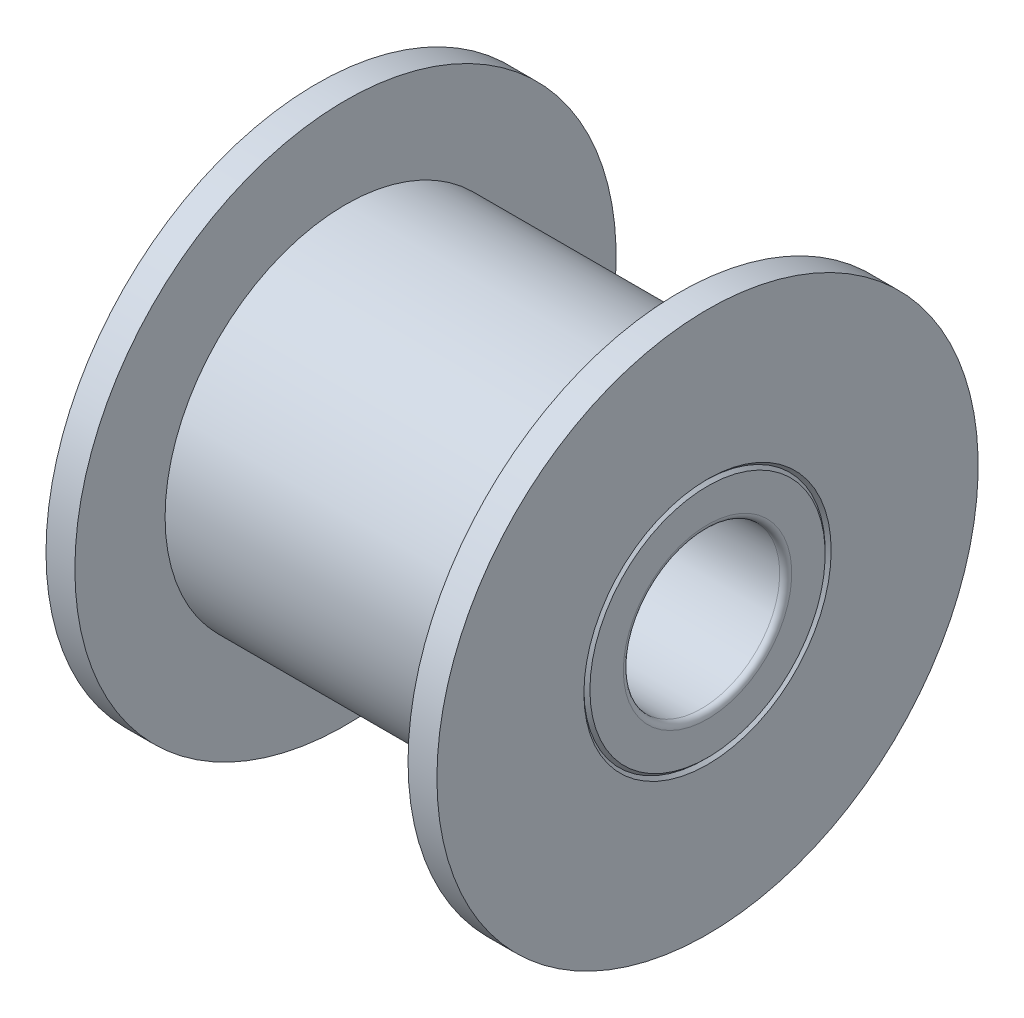
SolidWorks part; units mm, degrees
material "1.2311 (40CrMnMo7)"
ref_plane "Front" through (0, 0, 0) normal (0, 0, 1) x (1, 0, 0)
ref_plane "Top" through (0, 0, 0) normal (0, 1, 0) x (1, 0, 0)
ref_plane "Right" through (0, 0, 0) normal (1, 0, 0) x (0, 0, -1)
sketch "Sketch 1" plane through (0, 0, 0) normal (0, 0, 1) x (1, 0, 0)
  line L0 (1, 7.5) -> (1, 2.6118)
  line L1 (1, -1.5) -> (14, -1.5) construction
  line L2 (1, 7.5) -> (1.96, 7.5)
  line L4 (1.96, 4.5) -> (13.04, 4.5)
  line L5 (13.04, 4.5) -> (13.04, 7.5)
  line L6 (13.04, 7.5) -> (14, 7.5)
  line L7 (14, 1.1) -> (14, 2.4118)
  line L8 (14, 2.4118) -> (13.9, 2.5118)
  line L9 (13.9, 2.5118) -> (14, 2.6118)
  line L10 (14, 2.6118) -> (14, 7.5)
  line L11 (14, 1.1) -> (1, 1.1)
  line L12 (1.96, 7.5) -> (1.96, 4.5)
  line L14 (1, 2.3882) -> (1.0866, 2.5)
  line L15 (1.0866, 2.5) -> (1, 2.6118)
  line L16 (1, 2.3882) -> (1, 1.1)
  dimension "D1" = 6
  dimension "D2" = 0.96
  dimension "D3" = 2.6
  dimension "D4" = 13
  dimension "D5" = 0.1
  dimension "D6" = 5
  dimension "D7" = 9
revolve "Body" add sketch "Sketch 1" angle 360 about L1 region at (7.5, 3.1692, 0)
sketch "Sketch 3" plane through (1.96, 0, 0) normal (1, 0, 0) x (0, 0, -1)
  line L0 (0, 0) -> (9.7637, 0) construction
  circle A18 centre (0, 5.855) radius 0.55
  point P45 (0, 0)
ref_axis "Axis1" through (-2.8, 0, 0) along (1, 0, 0)
fillet "Fillet1" radius 0.2 2 edges at (14, -1.5, 2.6) (1, -1.5, 2.6)
sketch "Sketch1" plane through (14, 0, 0) normal (1, 0, 0) x (0, 0, -1)
  point P0 (0, -1.5)
